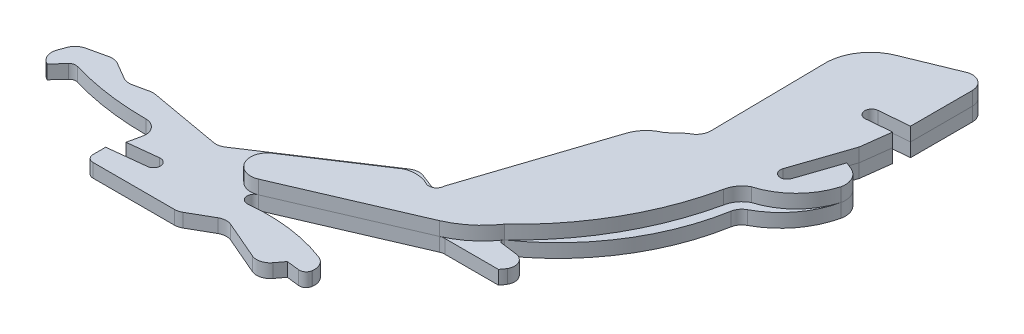
SolidWorks part; units mm, degrees
ref_plane "Front Plane" through (0, 0, 0) normal (0, 0, 1) x (1, 0, 0)
ref_plane "Top Plane" through (0, 0, 0) normal (0, 1, 0) x (1, 0, 0)
ref_plane "Right Plane" through (0, 0, 0) normal (1, 0, 0) x (0, 0, -1)
sketch "Sketch2" plane through (0, 0, 0) normal (0, 1, 0) x (1, 0, 0)
  line L0 (104.8617, 51.61) -> (96.2857, 51.61)
  line L1 (96.2857, 48.61) -> (104.8617, 48.61)
  line L2 (104.8617, 48.61) -> (104.8617, 42.36)
  line L3 (107.0706, 39.34) -> (104.0266, 29.4584)
  line L4 (101.1595, 30.3416) -> (104.8617, 42.36)
  line L5 (105.5312, 18.3607) -> (111.09, 27.1258)
  line L6 (104.8617, 51.61) -> (107.0706, 55.46)
  line L7 (89.7728, 69.8362) -> (57.4, 86.17)
  line L8 (41.6529, 73.6621) -> (36.03, 31.3784)
  line L9 (36.03, 31.3784) -> (29.1482, 28.9869)
  line L10 (29.1482, 28.9869) -> (21.9915, 21.0198)
  line L11 (21.9915, 21.0198) -> (8.1869, 15.1615)
  line L12 (0, 0) -> (0, 4.28)
  line L13 (0, 4.28) -> (8.2554, 5.2)
  line L14 (7.9231, 8.1815) -> (-3.1214, 6.9507)
  line L15 (-3.1214, 6.9507) -> (-7.4992, 8.4826)
  line L16 (-7.4992, 8.4826) -> (-11.8276, 7.2216)
  line L17 (-11.8276, 7.2216) -> (-19.2552, 11.2976)
  line L18 (-19.2552, 11.2976) -> (-23.2053, 10.8574)
  line L19 (-23.2053, 10.8574) -> (-22.2697, 7.6463)
  line L20 (-22.2697, 7.6463) -> (-24.8125, 7.2216)
  line L21 (0, 0) -> (20.16, 0)
  line L22 (20.16, 0) -> (27.0155, 3.9247)
  line L23 (27.0155, 3.9247) -> (38.9, -1.2)
  line L24 (38.9, -1.2) -> (41.66, 2.4827)
  line L25 (41.66, 2.4827) -> (45.9, 1.9915)
  line L26 (45.9, 1.9915) -> (46.4657, 5.8541)
  line L27 (25.83, 11.99) -> (49.95, 19.39)
  line L28 (49.95, 19.39) -> (57.13, 16.32)
  line L29 (57.13, 16.32) -> (61.9358, 23.0276)
  line L30 (61.9358, 23.0276) -> (67.6517, 44.29)
  arc A0 (96.2857, 51.61) -> (96.2857, 48.61) centre (96.2857, 50.11) ccw
  arc A1 (107.0706, 39.34) -> (111.09, 27.1258) centre (97.2099, 29.3266) cw
  arc A2 (104.0266, 29.4584) -> (101.1595, 30.3416) centre (102.5931, 29.9) cw
  arc A3 (107.0706, 55.46) -> (93.2591, 66.4439) centre (93.6334, 52.7391) ccw
  arc A4 (93.2591, 66.4439) -> (89.7728, 69.8362) centre (93.1665, 69.8362) cw
  arc A5 (57.4, 86.17) -> (41.6529, 73.6621) centre (56.0104, 71.7528) ccw
  arc A6 (8.1869, 15.1615) -> (-17.7049, 14.5311) centre (-5.6083, 49.7338) cw
  arc A7 (8.2554, 5.2) -> (7.9231, 8.1815) centre (8.0892, 6.6908) ccw
  arc A8 (-24.8125, 7.2216) -> (-27.5, 15.12) centre (-19.6156, 13.3963) cw
  arc A9 (-27.5, 15.12) -> (-17.7049, 14.5311) centre (-22.91, 9.71) cw
  arc A10 (46.4657, 5.8541) -> (26.4315, 9.0647) centre (30.5748, -29.1928) ccw
  arc A11 (26.4315, 9.0647) -> (25.83, 11.99) centre (26.27, 10.556) cw
  arc A12 (67.6517, 44.29) -> (105.5312, 18.3607) centre (122.4523, 83.7134) ccw
  point P4 (0, 0)
  point P9 (102.1515, 28.4665)
  point P12 (94.7857, 50.11)
  point P13 (-27.5, 15.12)
  point P72 (9.58, 6.8569)
  dimension "D6" = 1.5
  dimension "D11" = 1.5
  dimension "D32" = 14.0535
  dimension "D33" = 13.7098
  dimension "D34" = 3.3937
  dimension "D35" = 14.484
  dimension "D36" = 37.223
  dimension "D37" = 8.0706
  dimension "D38" = 7.0948
  dimension "D39" = 38.4812
  dimension "D40" = 67.5078
  dimension "D75" = 1.5
  dimension "D1" = 51.61
  dimension "D2" = 111.09
  dimension "D3" = 10.076
  dimension "D4" = 27.5
  dimension "D5" = 15.12
  dimension "D7" = 29.9
  dimension "D8" = 39.34
  dimension "D9" = 6.25
  dimension "D10" = 102.5931
  dimension "D12" = 4.28
  dimension "D13" = 20.16
  dimension "D14" = 5.14
  dimension "D15" = 1.2
  dimension "D16" = 45.9
  dimension "D17" = 38.9
  dimension "D18" = 86.17
  dimension "D19" = 9.58
  dimension "D20" = 5.2
  dimension "D21" = 11.99
  dimension "D22" = 16.32
  dimension "D23" = 57.13
  dimension "D24" = 49.95
  dimension "D25" = 26.27
  dimension "19.39" = 19.39
  dimension "D26" = 84.9
  dimension "D27" = 63.53
  dimension "D28" = 37.21
  dimension "D29" = 44.29
  dimension "D30" = 3.85
  dimension "D31" = 20
  dimension "D41" = 8.1869
  dimension "D42" = 21.9915
  dimension "D43" = 26.4315
  dimension "D44" = 27.0155
  dimension "D45" = 29.1482
  dimension "D46" = 41.6529
  dimension "D47" = 41.66
  dimension "D48" = 46.4657
  dimension "D49" = 56.0104
  dimension "D50" = 61.9358
  dimension "D51" = 67.6517
  dimension "D52" = 89.7728
  dimension "D53" = 97.2099
  dimension "D54" = 105.5312
  dimension "D55" = 122.4523
  dimension "D56" = 3.1214
  dimension "D57" = 5.6083
  dimension "D58" = 7.4992
  dimension "D59" = 11.8276
  dimension "D60" = 17.7049
  dimension "D61" = 19.2552
  dimension "D62" = 19.6156
  dimension "D63" = 22.2697
  dimension "D64" = 22.91
  dimension "D65" = 23.2053
  dimension "D66" = 24.8125
  dimension "D67" = 1.9915
  dimension "D68" = 2.4827
  dimension "D69" = 7.6463
  dimension "D70" = 8.4826
  dimension "D71" = 11.2976
  dimension "D72" = 21.0198
  dimension "D73" = 23.0276
  dimension "D74" = 28.9869
sketch "Sketch3" plane through (0, 0, 0) normal (0, 1, 0) x (1, 0, 0)
  line L0 (7.9231, 8.1815) -> (1.2884, 7.4422)
  line L1 (45.9, 1.9915) -> (46.4657, 5.8541) construction
  line L2 (41.66, 2.4827) -> (45.9, 1.9915) construction
  line L3 (38.9, -1.2) -> (41.66, 2.4827) construction
  line L4 (27.0155, 3.9247) -> (38.9, -1.2) construction
  line L5 (20.16, 0) -> (27.0155, 3.9247) construction
  line L6 (0, 4.28) -> (8.2554, 5.2) construction
  line L7 (0, 0) -> (0, 4.28) construction
  line L8 (0, 0) -> (20.16, 0) construction
  line L9 (1.2884, 7.4422) -> (2.7682, 14.19)
  line L10 (45.9, 1.9915) -> (46.4657, 5.8541)
  line L11 (41.66, 2.4827) -> (45.9, 1.9915)
  line L12 (38.9, -1.2) -> (41.66, 2.4827)
  line L13 (27.0155, 3.9247) -> (38.9, -1.2)
  line L14 (20.16, 0) -> (27.0155, 3.9247)
  line L15 (0, 4.28) -> (8.2554, 5.2)
  line L16 (0, 0) -> (0, 4.28)
  line L17 (0, 0) -> (20.16, 0)
  line L18 (-19.3597, 16.8) -> (-22.2168, 13.6663)
  line L19 (-22.2168, 13.6663) -> (-24.8203, 14.623)
  line L20 (-24.8203, 14.623) -> (-22.6465, 20.5386)
  line L21 (-22.6465, 20.5386) -> (-15.7038, 22.1118)
  line L22 (-15.7038, 22.1118) -> (-10.0733, 18.8185)
  line L23 (-10.0733, 18.8185) -> (-5.1865, 19.8808)
  line L24 (-5.1865, 19.8808) -> (12.13, 16.8)
  line L25 (12.13, 16.8) -> (38.76, 34.29)
  line L26 (87.31, 93.5914) -> (80.7227, 93.015)
  line L27 (80.9841, 90.0265) -> (86.4632, 90.5058)
  line L28 (87.31, 93.5914) -> (87.31, 111.63)
  line L29 (87.31, 111.63) -> (66.29, 103.0079)
  line L32 (66.29, 103.0079) -> (64.5523, 69.7569)
  line L33 (64.5523, 69.7569) -> (56.0586, 66.407)
  line L34 (56.0586, 66.407) -> (44.7, 32)
  line L35 (44.7, 32) -> (38.76, 34.29)
  line L36 (25.83, 11.99) -> (54.05, 24.15)
  line L37 (54.05, 24.15) -> (66.29, 24.15)
  line L38 (68.0387, 28.663) -> (60.2978, 29.686)
  line L39 (87.31, 79.61) -> (91.6185, 77.8876)
  line L40 (87.31, 79.61) -> (84.2303, 70.5437)
  line L41 (81.3897, 71.5086) -> (85.6329, 84)
  line L42 (85.6329, 84) -> (86.4632, 90.5058)
  arc A0 (25.83, 11.99) -> (26.4315, 9.0647) centre (26.27, 10.556) ccw construction
  arc A1 (46.4657, 5.8541) -> (26.4315, 9.0647) centre (30.5748, -29.1928) ccw construction
  arc A3 (25.83, 11.99) -> (26.4315, 9.0647) centre (26.27, 10.556) ccw
  arc A4 (46.4657, 5.8541) -> (26.4315, 9.0647) centre (30.5748, -29.1928) ccw
  arc A5 (8.2554, 5.2) -> (7.9231, 8.1815) centre (8.0892, 6.6908) ccw
  arc A6 (2.7682, 14.19) -> (-19.3597, 16.8) centre (-1.1426, 76.1401) cw
  arc A7 (80.7227, 93.015) -> (80.9841, 90.0265) centre (80.8534, 91.5207) ccw
  arc A8 (66.29, 24.15) -> (68.0387, 28.663) centre (61.3409, 28.663) ccw
  arc A9 (60.2978, 29.686) -> (80.9841, 62.2084) centre (34.8127, 68.7363) ccw
  arc A10 (91.6185, 77.8876) -> (80.9841, 62.2084) centre (74.0824, 78.3355) cw
  arc A11 (84.2303, 70.5437) -> (81.3897, 71.5086) centre (82.81, 71.0261) cw
  point P20 (87.31, 111.63)
  point P28 (87.31, 79.61)
  point P40 (79.3591, 91.39)
  point P55 (0, 2.14)
  point P77 (9.58, 6.8569)
  point P90 (82.3275, 69.6058)
  dimension "D5" = 1.5
  dimension "D22" = 62.0734
  dimension "D23" = 6.6978
  dimension "D24" = 46.6306
  dimension "D25" = 17.5418
  dimension "D1" = 111.63
  dimension "D2" = 87.31
  dimension "D3" = 79.61
  dimension "D4" = 17.97
  dimension "D6" = 8.25
  dimension "95" = 95
  dimension "D7" = 54.05
  dimension "D8" = 44.7
  dimension "D9" = 32
  dimension "D10" = 24.15
  dimension "D11" = 16.8
  dimension "D12" = 2.55
  dimension "D13" = 38.76
  dimension "D14" = 2.29
  dimension "D15" = 66.29
  dimension "D16" = 4.64
  dimension "D17" = 23.46
  dimension "D18" = 82.81
  dimension "D19" = 84
  dimension "D20" = 5.5
  dimension "D21" = 14.19
  dimension "D26" = 1.2884
  dimension "D27" = 2.7682
  dimension "D28" = 34.8127
  dimension "D29" = 56.0586
  dimension "D30" = 60.2978
  dimension "D31" = 61.3409
  dimension "D32" = 64.5523
  dimension "D33" = 68.0387
  dimension "D34" = 74.0824
  dimension "D35" = 1.1426
  dimension "D36" = 13.6663
  dimension "D37" = 14.623
  dimension "D38" = 91.6185
  dimension "D39" = 18.8185
  dimension "D40" = 5.1865
  dimension "D41" = 10.0733
  dimension "D42" = 15.7038
  dimension "D43" = 19.8808
  dimension "D44" = 22.2168
  dimension "D45" = 22.6465
  dimension "D46" = 24.8203
  dimension "D48" = 22.1118
  dimension "D49" = 66.407
  dimension "D51" = 69.7569
  dimension "D53" = 103.0079
extrude "Boss-Extrude1" add sketch "Sketch3" along normal blind 3
fillet "Fillet1" radius 3 13 edges at (-24.8203, 1.5, -14.623) (80.9841, 1.5, -62.2084) (20.16, 1.5, 0) (46.4657, 1.5, -5.8541) (38.9, 1.5, 1.2) (27.0155, 1.5, -3.9247) (38.76, 1.5, -34.29) (12.13, 1.5, -16.8) (-5.1865, 1.5, -19.8808) (-10.0733, 1.5, -18.8185) (-15.7038, 1.5, -22.1118) (-22.6465, 1.5, -20.5386) (2.7682, 1.5, -14.19)
fillet "Fillet2" radius 1.5 4 edges at (64.5523, 1.5, -69.7569) (45.9, 1.5, -1.9915) (0, 1.5, 0) (-19.3597, 1.5, -16.8)
fillet "Fillet3" radius 10 2 edges at (56.0586, 1.5, -66.407) (66.29, 1.5, -103.0079)
fillet "Fillet4" radius 3 1 edges at (87.31, 1.5, -111.63)
fillet "Fillet5" radius 4 1 edges at (91.6185, 1.5, -77.8876)
fillet "Fillet6" radius 2.5 2 edges at (68.0387, 1.5, -28.663) (54.05, 1.5, -24.15)
fillet "Fillet7" radius 0.5 1 edges at (60.2978, 1.5, -29.686)
sketch "Sketch5" plane through (0, 3, 0) normal (0, 1, 0) x (1, 0, 0)
  line L0 (37.4719, 33.444) -> (13.1275, 17.4551) construction
  line L1 (87.31, 79.61) -> (84.2303, 70.5437) construction
  line L2 (57.4386, 61.0176) -> (47.5488, 31.0596)
  line L3 (57.4386, 61.0176) -> (47.5488, 31.0596)
  line L4 (81.3897, 71.5086) -> (85.6329, 84) construction
  line L5 (85.6329, 84) -> (86.4632, 90.5058) construction
  line L6 (87.31, 79.61) -> (84.2303, 70.5437)
  line L7 (81.3897, 71.5086) -> (85.6329, 84)
  line L8 (85.6329, 84) -> (86.4632, 90.5058)
  line L9 (83.1715, 109.9324) -> (72.1508, 105.4119) construction
  line L10 (87.31, 93.5914) -> (87.31, 107.1569) construction
  line L11 (80.7227, 93.015) -> (87.31, 93.5914) construction
  line L12 (86.4632, 90.5058) -> (80.9841, 90.0265) construction
  line L13 (83.1715, 109.9324) -> (72.1508, 105.4119)
  line L14 (87.31, 93.5914) -> (87.31, 107.1569)
  line L15 (80.7227, 93.015) -> (87.31, 93.5914)
  line L16 (86.4632, 90.5058) -> (80.9841, 90.0265)
  line L17 (64.2787, 67.8215) -> (61.5176, 65.3351)
  line L18 (66.3003, 70.6314) -> (65.9594, 96.6819)
  line L20 (25.83, 11.99) -> (53.5764, 23.9459) construction
  line L22 (39.8372, 29.8426) -> (22.3877, 18.3821)
  line L23 (25.83, 11.99) -> (53.5764, 23.9459)
  line L24 (88.7674, 79.0274) -> (87.31, 79.61) construction
  line L25 (88.7674, 79.0274) -> (87.31, 79.61)
  arc A0 (81.3598, 64.6027) -> (91.1817, 74.4204) centre (77.2314, 78.5549) ccw
  arc A1 (78.7758, 61.0463) -> (61.3879, 30.4195) centre (20.6563, 73.7936) cw
  arc A2 (61.3879, 30.4195) -> (53.5764, 23.9459) centre (46.1457, 40.862) cw
  arc A3 (61.5176, 65.3351) -> (57.4386, 61.0176) centre (64.0858, 58.8232) ccw
  arc A4 (61.5176, 65.3351) -> (57.4386, 61.0176) centre (64.0858, 58.8232) ccw
  arc A5 (81.3897, 71.5086) -> (84.2303, 70.5437) centre (82.81, 71.0261) ccw construction
  arc A6 (81.3598, 64.6027) -> (78.7758, 61.0463) centre (83.701, 60.1848) ccw
  arc A7 (81.3598, 64.6027) -> (78.7758, 61.0463) centre (83.701, 60.1848) ccw
  arc A8 (81.3897, 71.5086) -> (84.2303, 70.5437) centre (82.81, 71.0261) ccw
  arc A9 (72.1508, 105.4119) -> (65.9594, 96.6819) centre (75.9458, 96.16) ccw construction
  arc A10 (87.31, 107.1569) -> (83.1715, 109.9324) centre (84.31, 107.1569) ccw construction
  arc A11 (80.7227, 93.015) -> (80.9841, 90.0265) centre (80.8534, 91.5207) ccw construction
  arc A12 (72.1508, 105.4119) -> (65.9594, 96.6819) centre (75.9458, 96.16) ccw
  arc A13 (87.31, 107.1569) -> (83.1715, 109.9324) centre (84.31, 107.1569) ccw
  arc A14 (80.7227, 93.015) -> (80.9841, 90.0265) centre (80.8534, 91.5207) ccw
  arc A17 (64.2787, 67.8215) -> (66.3003, 70.6314) centre (63.1047, 70.7984) ccw
  arc A18 (64.2787, 67.8215) -> (66.3003, 70.6314) centre (63.1047, 70.7984) ccw
  arc A19 (45.0858, 29.5439) -> (39.8372, 29.8426) centre (42.1264, 23.8033) ccw
  arc A20 (45.0858, 29.5439) -> (47.5488, 31.0596) centre (45.8598, 31.0452) ccw
  arc A21 (25.83, 11.99) -> (22.3877, 18.3821) centre (24.3881, 15.3364) cw
  arc A24 (91.1817, 74.4204) -> (88.7674, 79.0274) centre (87.2826, 75.3132) ccw construction
  arc A25 (91.1817, 74.4204) -> (88.7674, 79.0274) centre (87.2826, 75.3132) ccw
  point P0 (0, 0)
  dimension "D7" = 14.5501
  dimension "D8" = 59.5011
  dimension "D9" = 18.4762
  dimension "D10" = 6.4585
  dimension "D11" = 1.689
  dimension "D12" = 25.9221
  dimension "D5" = 4.3087
  dimension "D13" = 41.1643
  dimension "D14" = 41.4502
  dimension "D6" = 42.1264
  dimension "D1" = 3
  dimension "D2" = 3
  dimension "D3" = 2
  dimension "D4" = 1.7
extrude "Boss-Extrude2" add sketch "Sketch5" along normal blind 3 separate body
